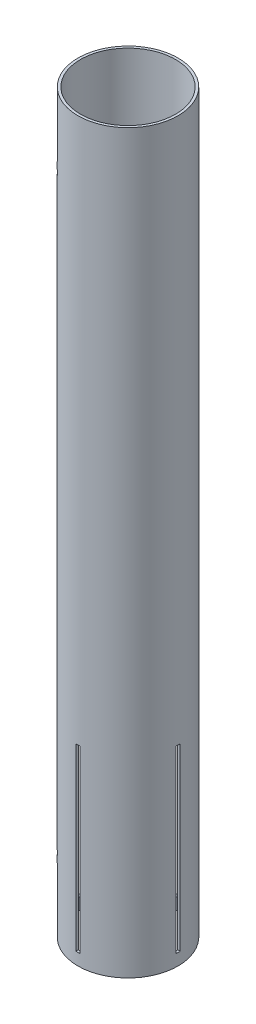
SolidWorks part; units mm, degrees
material "S-Glass Fiber"
ref_plane "Front Plane" through (0, 0, 0) normal (0, 0, 1) x (1, 0, 0)
ref_plane "Top Plane" through (0, 0, 0) normal (0, 1, 0) x (1, 0, 0)
ref_plane "Right Plane" through (0, 0, 0) normal (1, 0, 0) x (0, 0, -1)
ref_axis "ROCKET AXIS" through (0, -25, 0) along (0, 1, 0)
sketch "Sketch1" plane through (0, 0, 0) normal (0, 1, 0) x (1, 0, 0)
  circle A0 centre (0, 0) radius 32.258
  circle A1 centre (0, 0) radius 33.9725
  dimension "D1" = 64.516
  dimension "D2" = 67.945
extrude "BULK" add sketch "Sketch1" along normal blind 500
ref_plane "LAUNCH LUG PLANE" through (0, 0, 0) normal (-0.7071, 0, 0.7071) x (0.7071, 0, 0.7071)
sketch "Sketch2" plane through (0, 0, 0) normal (-0.7071, 0, 0.7071) x (0.7071, 0, 0.7071)
  circle A0 centre (0, 50) radius 1.75
  circle A1 centre (0, 450) radius 1.75
  point P4 (0, 0)
  dimension "D1" = 3.5
  dimension "D2" = 50
  dimension "D3" = 450
extrude "LAUNCH LUG SCREW HOLES" cut sketch "Sketch2" along normal through all
sketch "Sketch3" plane through (0, 0, 0) normal (0, 0, 1) x (1, 0, 0)
  line L1 (-1.5, 130) -> (1.5, 130)
  line L2 (-1.5, 130) -> (-1.5, 8)
  line L3 (-1.5, 8) -> (1.5, 8)
  line L4 (1.5, 130) -> (1.5, 8)
  point P4 (0, 8)
  dimension "D1" = 8
  dimension "D2" = 3
  dimension "D3" = 122
extrude "THRU WALL FIN CUTS" cut sketch "Sketch3" against normal through all both and the other way through all
pattern_circular "THRU WALL FIN CUT PATTERN" count 2 every 90 about axis through (0, -25, 0) along (0, 1, 0) of "THRU WALL FIN CUTS"
